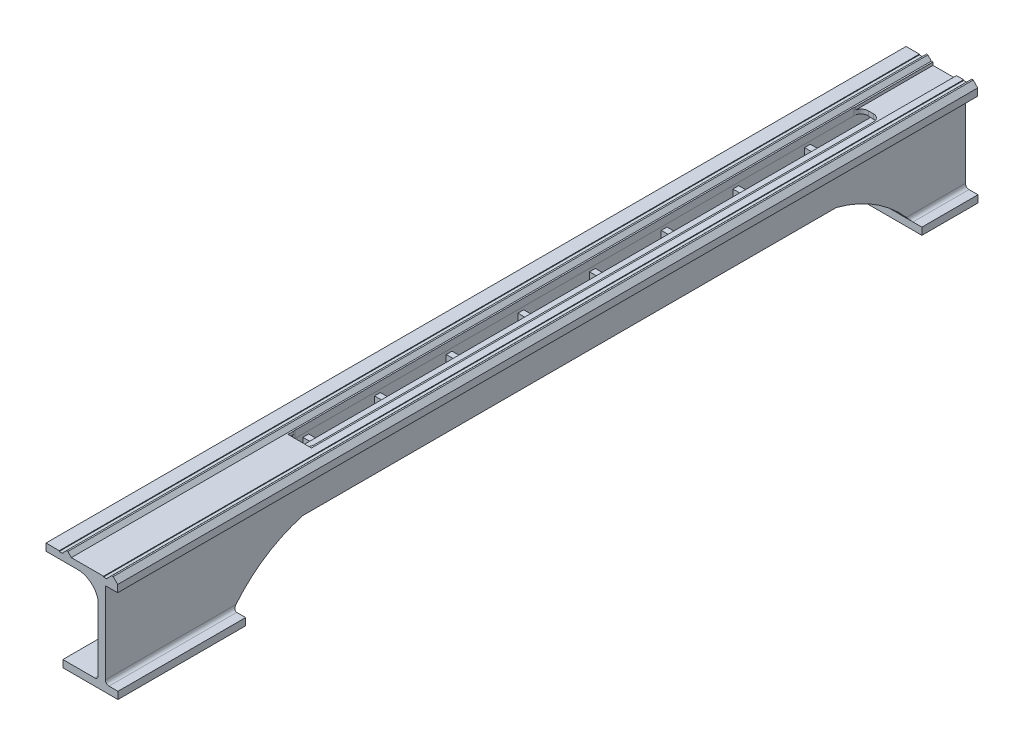
SolidWorks part; units mm, degrees
ref_plane "Front Plane" through (0, 0, 0) normal (0, 0, 1) x (1, 0, 0)
ref_plane "Top Plane" through (0, 0, 0) normal (0, 1, 0) x (1, 0, 0)
ref_plane "Right Plane" through (0, 0, 0) normal (1, 0, 0) x (0, 0, -1)
sketch "Sketch1" plane through (0, 0, 0) normal (0, 0, 1) x (1, 0, 0)
  line L0 (-31.5551, 31.2902) -> (-37.8538, 37.7187)
  line L2 (-131.555, 31.42) -> (-131.555, 21.42)
  line L4 (-31.5551, 31.2902) -> (-31.5551, 21.2902)
  line L5 (-37.8538, 37.7187) -> (-39.8538, 37.7187)
  line L6 (-39.8538, 37.7187) -> (-46.2824, 31.42)
  line L7 (-46.2824, 31.42) -> (-46.2824, 30.42)
  line L8 (-46.2824, 30.42) -> (-51.2824, 30.42)
  line L9 (-51.2824, 30.42) -> (-51.2824, 31.42)
  line L10 (-51.2824, 31.42) -> (-96.2063, 31.42)
  line L14 (-96.2063, 31.42) -> (-101.1053, 36.42)
  line L15 (-101.1053, 36.42) -> (-103.1053, 36.42)
  line L16 (-103.1053, 36.42) -> (-108.055, 31.4703)
  line L17 (-108.055, 31.4703) -> (-108.055, 30.42)
  line L18 (-108.055, 30.42) -> (-113.055, 30.42)
  line L19 (-113.055, 30.42) -> (-113.055, 31.42)
  line L20 (-113.055, 31.42) -> (-131.555, 31.42)
  line L21 (-131.555, 21.42) -> (-87.3496, 21.42)
  line L22 (-31.5551, 21.2902) -> (-48.7011, 21.2902)
  line L23 (-48.7011, 21.2902) -> (-48.7011, -92.58)
  line L24 (-43.7011, -97.58) -> (-31.1954, -97.58)
  line L25 (-31.1954, -97.58) -> (-31.1954, -107.58)
  line L26 (-31.1954, -107.58) -> (-108.01, -107.58)
  line L27 (-108.01, -107.58) -> (-108.01, -97.58)
  line L28 (-108.01, -97.58) -> (-63.7011, -97.58)
  line L29 (-58.7011, -92.58) -> (-58.7011, -1.9527)
  arc A0 (-87.3496, 21.42) -> (-58.7011, -1.9527) centre (-87.3496, -7.8239) cw
  arc A1 (-48.7011, -92.58) -> (-43.7011, -97.58) centre (-43.7011, -92.58) ccw
  arc A2 (-63.7011, -97.58) -> (-58.7011, -92.58) centre (-63.7011, -92.58) ccw
  point P30 (-48.7011, -97.58)
  dimension "D17" = 5
  dimension "D1" = 100
  dimension "D2" = 7
  dimension "D3" = 2
  dimension "D4" = 5
  dimension "D5" = 18.5
  dimension "D6" = 5
  dimension "D7" = 10
  dimension "D8" = 135
  dimension "D9" = 9
  dimension "D10" = 9
  dimension "D11" = 2
  dimension "D12" = 7
  dimension "D13" = 10
  dimension "D14" = 5
  dimension "D15" = 10
  dimension "D16" = 139
  dimension "D18" = 10
  dimension "D19" = 1
extrude "Boss-Extrude1" add sketch "Sketch1" along normal blind 1200
sketch "Sketch2" plane through (0, 20.7647, 0) normal (0, 1, 0) x (1, 0, 0)
  line L0 (-94.1707, -1200) -> (-94.1707, 0) construction
  line L1 (-84.1707, -100) -> (-77.1707, -100)
  line L2 (-94.1707, -110) -> (-94.1707, -890)
  line L3 (-84.1707, -900) -> (-77.1707, -900)
  line L4 (-67.1707, -110) -> (-67.1707, -890)
  line L5 (-67.1707, -1200) -> (-67.1707, 0) construction
  line L6 (-51.2824, 0) -> (-96.2063, 0) construction
  arc A0 (-94.1707, -890) -> (-84.1707, -900) centre (-84.1707, -890) ccw
  arc A1 (-77.1707, -900) -> (-67.1707, -890) centre (-77.1707, -890) ccw
  arc A2 (-77.1707, -100) -> (-67.1707, -110) centre (-77.1707, -110) cw
  arc A3 (-84.1707, -100) -> (-94.1707, -110) centre (-84.1707, -110) ccw
  point P12 (-67.1707, -900)
  point P15 (-67.1707, -100)
  point P18 (-94.1707, -100)
  dimension "D2" = 10
  dimension "D1" = 800
  dimension "D3" = 100
extrude "Cut-Extrude1" cut sketch "Sketch2" along normal blind 800
sketch "Sketch3" plane through (0, 0, 1200) normal (0, 0, 1) x (1, 0, 0)
  line L1 (-61.1129, 27.3205) -> (-93.9675, 27.3205)
  line L2 (-61.1129, 27.3205) -> (-61.1129, 32.1773)
  line L3 (-61.1129, 32.1773) -> (-93.9675, 32.1773)
  line L4 (-93.9675, 27.3205) -> (-93.9675, 32.1773)
extrude "Cut-Extrude2" cut sketch "Sketch3" against normal blind 900 from offset 300 offset against normal yes
sketch "Sketch5" plane through (0, 0, 0) normal (0, 0, -1) x (-1, 0, 0)
  line L1 (101.3003, -90.5589) -> (94.9198, -90.5589)
  line L2 (101.3003, -90.5589) -> (101.3003, 27.7967)
  line L3 (101.3003, 27.7967) -> (94.9198, 27.7967)
  line L4 (94.9198, -90.5589) -> (94.9198, 27.7967)
extrude "Boss-Extrude2" add sketch "Sketch5" against normal blind 1100
sketch "Sketch6" plane through (-101.3003, 0, 0) normal (-1, 0, 0) x (0, 0, 1)
  line L1 (70.1556, 16.5847) -> (78.2516, 16.5847)
  line L2 (70.1556, 16.5847) -> (70.1556, -47.4448)
  line L3 (70.1556, -47.4448) -> (78.2516, -47.4448)
  line L4 (78.2516, 16.5847) -> (78.2516, -47.4448)
extrude "Boss-Extrude3" add sketch "Sketch6" against normal blind 50
pattern_linear "LPattern1" count 10 spacing 100 along (0, 0, 1) of "Boss-Extrude3"
sketch "Sketch4" plane through (-31.5551, 0, 0) normal (1, 0, 0) x (0, 0, -1)
  line L0 (-1021.7946, -97.58) -> (-1021.7946, -107.58)
  line L1 (-1200, -97.58) -> (0, -97.58) construction
  line L2 (-1200, -107.58) -> (0, -107.58) construction
  line L3 (-1021.7946, -107.58) -> (-1021.7946, -177.9566)
  line L4 (-1021.7946, -177.9566) -> (-78.2516, -177.9566)
  line L5 (-78.2516, -177.9566) -> (-78.2516, -97.58)
  line L6 (-924.3184, -31.7513) -> (-180.0688, -31.7513)
  arc A1 (-924.3184, -31.7513) -> (-1021.7946, -97.58) centre (-875.9115, -208.5137) ccw
  arc A2 (-180.0688, -31.7513) -> (-78.2516, -97.58) centre (-229.6539, -220.0994) cw
extrude "Cut-Extrude3" cut sketch "Sketch4" against normal blind 100 and the other way blind 10
